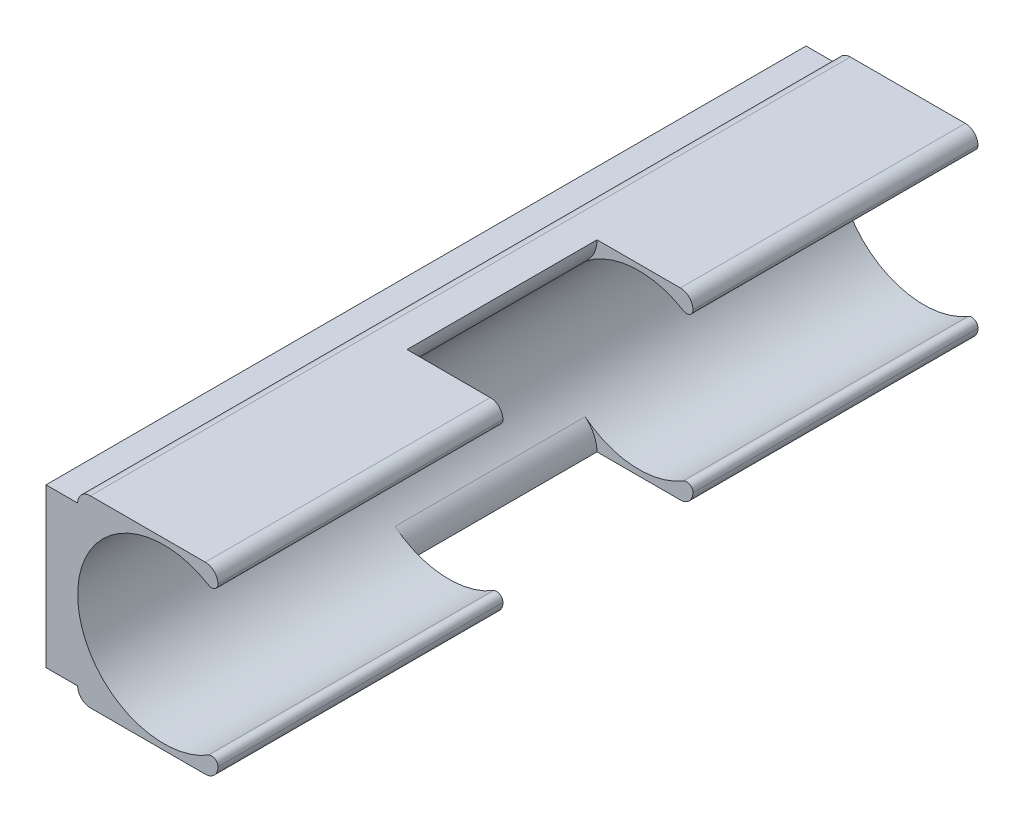
SolidWorks part; units mm, degrees
ref_plane "Front Plane" through (0, 0, 0) normal (0, 0, 1) x (1, 0, 0)
ref_plane "Top Plane" through (0, 0, 0) normal (0, 1, 0) x (1, 0, 0)
ref_plane "Right Plane" through (0, 0, 0) normal (1, 0, 0) x (0, 0, -1)
sketch "Sketch1" plane through (0, 0, 0) normal (1, 0, 0) x (0, 0, -1)
  line L1 (0, 0) -> (120, 0)
  line L2 (0, 0) -> (0, 25)
  line L3 (0, 25) -> (120, 25)
  line L4 (120, 0) -> (120, 25)
  dimension "D1" = 25
  dimension "D2" = 120
extrude "Base" add sketch "Sketch1" along normal blind 5
sketch "Sketch2" plane through (0, 0, 0) normal (0, 0, 1) x (1, 0, 0)
  line L0 (5, 25) -> (5, 0) construction
  line L1 (5, 25) -> (5, 0) construction
  line L2 (5, 12.5) -> (32.2, 12.5) construction
  line L5 (7, 27) -> (25.151, 27)
  line L6 (27.151, 23.0755) -> (27.151, 25)
  line L7 (7, -2) -> (25.151, -2)
  line L8 (27.151, 1.9245) -> (27.151, 0)
  line L9 (5, 0) -> (5, 25)
  circle A0 centre (18.6, 12.5) radius 13.6
  arc A1 (5, 25) -> (7, 27) centre (7, 25) cw
  arc A2 (25.151, 27) -> (27.151, 25) centre (25.151, 25) cw
  arc A3 (5, 0) -> (7, -2) centre (7, 0) ccw
  arc A4 (25.151, -2) -> (27.151, 0) centre (25.151, 0) ccw
  point P2 (5, 12.5)
  point P15 (7, 25)
  point P18 (27.151, 27)
  line M8 (5, 0) -> (5, 25)
  dimension "D1" = 27.2
  dimension "D4" = 2
  dimension "D5" = 2
  dimension "D2" = 20.25
  dimension "D3" = 2
extrude "Clip" add sketch "Sketch2" against normal up to surface (120 mm away) contours A2 L5 A1 A0 L6 M8 | L7 A4 L8 A0 A3 M8 region at (16.0755, 26.7353, 0) region at (12.6265, -0.0119, 0) up to face at (2.5, 12.5, -120)
sketch3d "3DSketch1"
  line L0 (0, 25, -120) -> (0, 25, 0) construction
  line L1 (0, 0, 0) -> (0, 0, -120) construction
  point P0 (0, 25, -60)
  point P1 (0, 0, -60)
ref_plane "Plane2" through (0, 0, -60) normal (0, 0, -1) x (-1, 0, 0)
sketch "Sketch3" plane through (0, 0, 0) normal (-1, 0, 0) x (0, 0, 1)
  line L0 (-120, 0) -> (-120, 25) construction
  line L1 (-60, 13.75) -> (-60, -13.75) construction
  circle A0 centre (-100, 12.5) radius 1.5
  circle A1 centre (-20, 12.5) radius 1.5
  point P4 (-120, 12.5)
  dimension "D1" = 3
  dimension "D2" = 20
extrude "ScrewHoles" cut sketch "Sketch3" against normal blind 3
fillet "RoundedCorners" radius 1 2 edges at (27.151, 1.9245, -60) (27.151, 23.0755, -60)
sketch "Sketch4" plane through (0, 0, -60) normal (0, 0, -1) x (-1, 0, 0)
  line L1 (-27.151, 27) -> (-12, 27)
  line L2 (-27.151, 27) -> (-27.151, -2)
  line L3 (-27.151, -2) -> (-12, -2)
  line L4 (-12, 27) -> (-12, -2)
  line L5 (-25.151, 27) -> (-7, 27) construction
  line L6 (-25.151, -2) -> (-7, -2) construction
  dimension "D1" = 5
extrude "FingerGap" cut sketch "Sketch4" against normal mid plane 30
fillet "FingerGroove" radius 5 2 edges at (12, 0.6088, -60) (12, 24.3912, -60)
